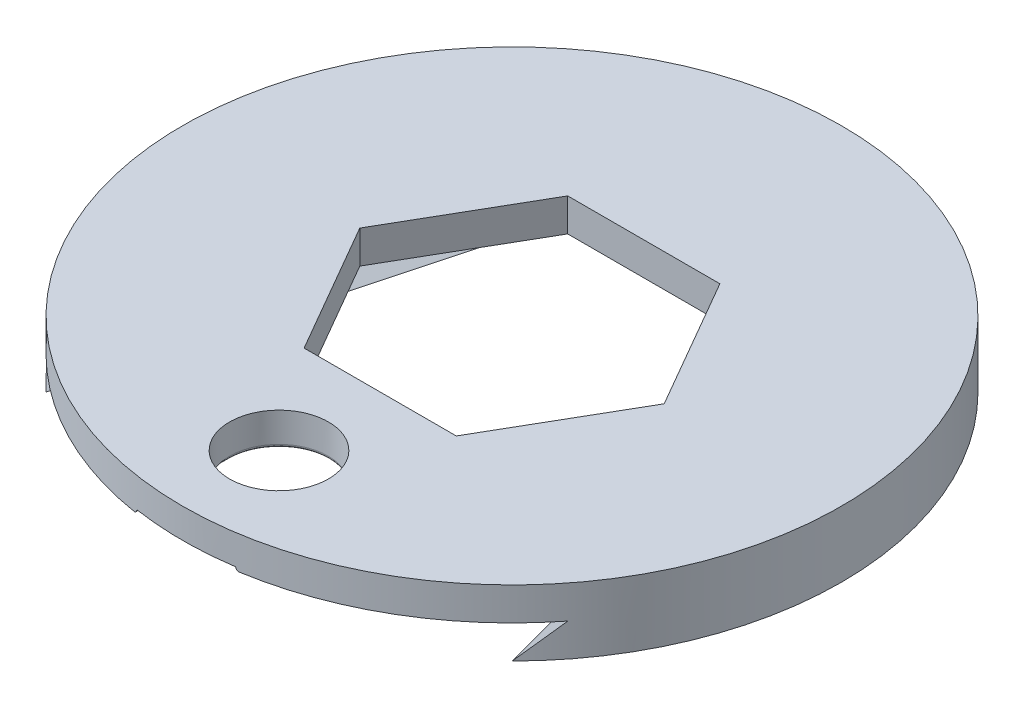
SolidWorks part; units mm, degrees
ref_plane "Front Plane" through (0, 0, 0) normal (0, 0, 1) x (1, 0, 0)
ref_plane "Top Plane" through (0, 0, 0) normal (0, 1, 0) x (1, 0, 0)
ref_plane "Right Plane" through (0, 0, 0) normal (1, 0, 0) x (0, 0, -1)
sketch "Sketch1" plane through (0, 0, 0) normal (0, 1, 0) x (1, 0, 0)
  line L0 (-35.3553, -35.3553) -> (-12.941, 48.2963)
  line L1 (-35.3553, -35.3553) -> (35.3553, -35.3553) construction
  line L2 (-35.3553, -35.3553) -> (-35.3553, 35.3553) construction
  line L3 (-35.3553, 35.3553) -> (35.3553, 35.3553) construction
  line L4 (35.3553, -35.3553) -> (35.3553, 35.3553) construction
  line L5 (-35.3553, -35.3553) -> (35.3553, 35.3553) construction
  line L6 (-35.3553, 35.3553) -> (35.3553, -35.3553) construction
  line L7 (0, 96.5926) -> (0, -94.4212) construction
  line L8 (35.3553, -35.3553) -> (12.941, 48.2963)
  circle A0 centre (0, 0) radius 50
  circle A1 centre (0, -35.3553) radius 7.5
  dimension "D1" = 100
  dimension "D3" = 15
  dimension "D2" = 15
extrude "Boss-Extrude1" add sketch "Sketch1" along normal blind 5 contours A0
extrude "Boss-Extrude2" add sketch "Sketch1<5>" against normal blind 5 contours L8 A0 | L0 A0 region at (-34.0499, 0, -9.1236) region at (34.0499, 0, -9.1236)
sketch "Sketch1<5>" plane through (0, 0, 0) normal (0, 1, 0) x (1, 0, 0) same geometry as "Sketch1"
draft "Draft1" type of draft neutral plane draft angle 45 faces to draft 2 face at (24.1481, -2.5, -6.4705) face at (-24.1481, -2.5, -6.4705) neutral plane through (0, -5, 0) neutral plane normal (0, -1, 0) reverse direction yes parameters "D1"=45
extrude "Cut-Extrude2" cut sketch "Sketch1<8>" against normal through all both and the other way through all contours A1 region at (0, 0, 35.3553)
sketch "Sketch1<8>" plane through (0, 0, 0) normal (0, 1, 0) x (1, 0, 0) same geometry as "Sketch1"
sketch "Sketch2" plane through (0, 0, 0) normal (0, -1, 0) x (1, 0, 0)
  line L1 (23.094, 0) -> (11.547, 20)
  line L2 (11.547, 20) -> (-11.547, 20)
  line L3 (-11.547, 20) -> (-23.094, 0)
  line L4 (-23.094, 0) -> (-11.547, -20)
  line L5 (-11.547, -20) -> (11.547, -20)
  line L6 (11.547, -20) -> (23.094, 0)
  circle A0 centre (0, 0) radius 20 construction
extrude "Cut-Extrude3" cut sketch "Sketch2" against normal through all
sketch "Sketch3" plane through (0, 0, 0) normal (0, -1, 0) x (1, 0, 0)
  line L0 (7.5, 35.3553) -> (7.5, 49.4343)
  line L1 (-7.5, 35.3553) -> (-7.5, 49.4343)
  circle A0 centre (0, 35.3553) radius 7.5 construction
  circle A1 centre (0, 35.3553) radius 7.5
  arc A2 (39.3305, 30.8725) -> (-39.3305, 30.8725) centre (0, 0) ccw construction
  arc A3 (39.3305, 30.8725) -> (-39.3305, 30.8725) centre (0, 0) ccw
  point P10 (7.5, 49.4343)
  circle M7 centre (0, 35.3553) radius 7.5
  arc M8 (39.3305, 30.8725) -> (-39.3305, 30.8725) centre (0, 0) ccw
extrude "Cut-Extrude4" cut sketch "Sketch3" against normal blind 0.5 contours L1 L0 M7 M8 region at (0, 0, 45.3669)
fillet "Fillet1" radius 0.5 3 edges at (0, 0, 27.8553) (-7.5, 0, 42.3948) (7.5, 0, 42.3948)
